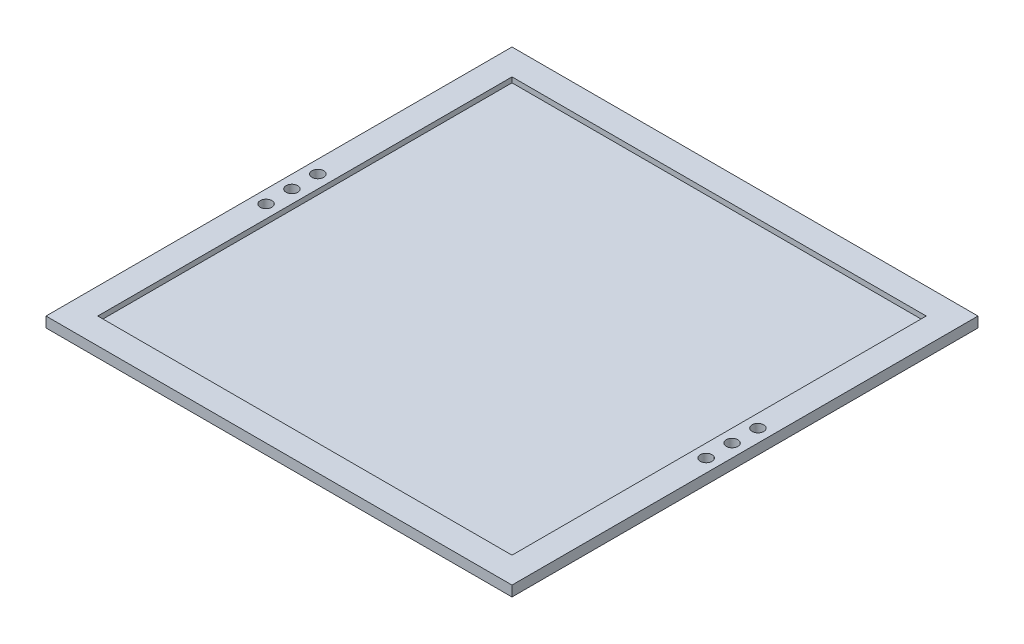
SolidWorks part; units mm, degrees
ref_plane "前视基准面" through (0, 0, 0) normal (0, 0, 1) x (1, 0, 0)
ref_plane "上视基准面" through (0, 0, 0) normal (0, 1, 0) x (1, 0, 0)
ref_plane "右视基准面" through (0, 0, 0) normal (1, 0, 0) x (0, 0, -1)
other "Configuration Table"
sketch "草图2" plane through (0, 0, 0) normal (0, 1, 0) x (1, 0, 0)
  line L0 (0, 0) -> (0, 80)
  line L1 (0, 80) -> (-80, 80)
  line L2 (-80, 80) -> (-80, -80)
  line L3 (-80, -80) -> (80, -80)
  line L4 (80, -80) -> (80, 80)
  line L5 (80, 80) -> (0, 80)
  line L6 (-80, 80) -> (-80, 90)
  line L7 (-80, 90) -> (80, 90)
  line L8 (80, 90) -> (90, 90)
  line L9 (90, 90) -> (90, -80)
  line L10 (90, -80) -> (90, -90)
  line L11 (90, -90) -> (-80, -90)
  line L12 (-80, -90) -> (-90, -90)
  line L13 (-90, -90) -> (-90, 90)
  line L14 (-90, 90) -> (-80, 90)
  dimension "D1" = 80
  dimension "D2" = 80
  dimension "D3" = 160
  dimension "D4" = 10
  dimension "D5" = 160
  dimension "D6" = 10
  dimension "D7" = 170
  dimension "D8" = 10
  dimension "D9" = 170
  dimension "D10" = 10
extrude "凸台-拉伸1" add sketch "草图2" along normal blind 2 contours L4 L5 L1 L2 L3 | L14 L13 L12 L11 L10 L9 L8 L7 L1 L5 L4 L3 L2 region at (40, 0, -77.7373) region at (0, 0, -87.4544)
extrude "凸台-拉伸2" add sketch "草图2<3>" along normal blind 4 contours L14 L13 L12 L11 L10 L9 L8 L7 L1 L5 L4 L3 L2 region at (0, 0, -87.4544)
sketch "草图2<3>" plane through (0, 0, 0) normal (0, 1, 0) x (1, 0, 0) same geometry as "草图2"
sketch "草图3" plane through (0, 4, 0) normal (0, 1, 0) x (1, 0, 0)
  line L0 (0, 0) -> (-90, 0)
  line L1 (-90, -90) -> (-90, 90) construction
  line L2 (0, 0) -> (90, 0)
  line L3 (90, 90) -> (90, -90) construction
  line L4 (-90, 0) -> (-80, 0)
  line L5 (-80, 80) -> (-80, -80) construction
  line L6 (-80, -80) -> (-80, -90)
  line L7 (90, -90) -> (-90, -90) construction
  line L8 (-90, -90) -> (-80, -90)
  line L9 (-85, -90) -> (-85, 90)
  line L10 (-90, 90) -> (90, 90) construction
  line L11 (0, 80) -> (0, -80)
  line L12 (-80, 80) -> (80, 80) construction
  line L13 (80, -80) -> (-80, -80) construction
  line L14 (-85, 0) -> (-85, 10)
  line L15 (-85, 0) -> (-85, -10)
  circle A0 centre (-85, 0) radius 2.25
  circle A1 centre (-85, 10) radius 2.25
  circle A2 centre (-85, -10) radius 2.25
  circle A3 centre (85, -10) radius 2.25
  circle A4 centre (85, 0) radius 2.25
  circle A5 centre (85, 10) radius 2.25
extrude "切除-拉伸1" cut sketch "草图3" against normal through all and the other way through all contours L9 A1 | L9 A1 | L4 A0 L9 | L9 A0 L4 | L4 A0 L15 | L15 A0 L4 | L9 A2 | L9 A2 | A5 | A4 L2 | A4 L2 | A3 region at (-84.0451, 4, 10) region at (-85.9549, 4, 10) region at (-85.9549, 4, -10) region at (-84.0451, 4, -10) region at (-84.0451, 4, 0.9549) region at (-84.0451, 4, -0.9549) region at (85, 4, -0.9549) region at (85, 4, 0.9549) region at (-85.9549, 4, 0.9549) region at (-85.9549, 4, -0.9549) region at (85, 4, 10) region at (85, 4, -10)
